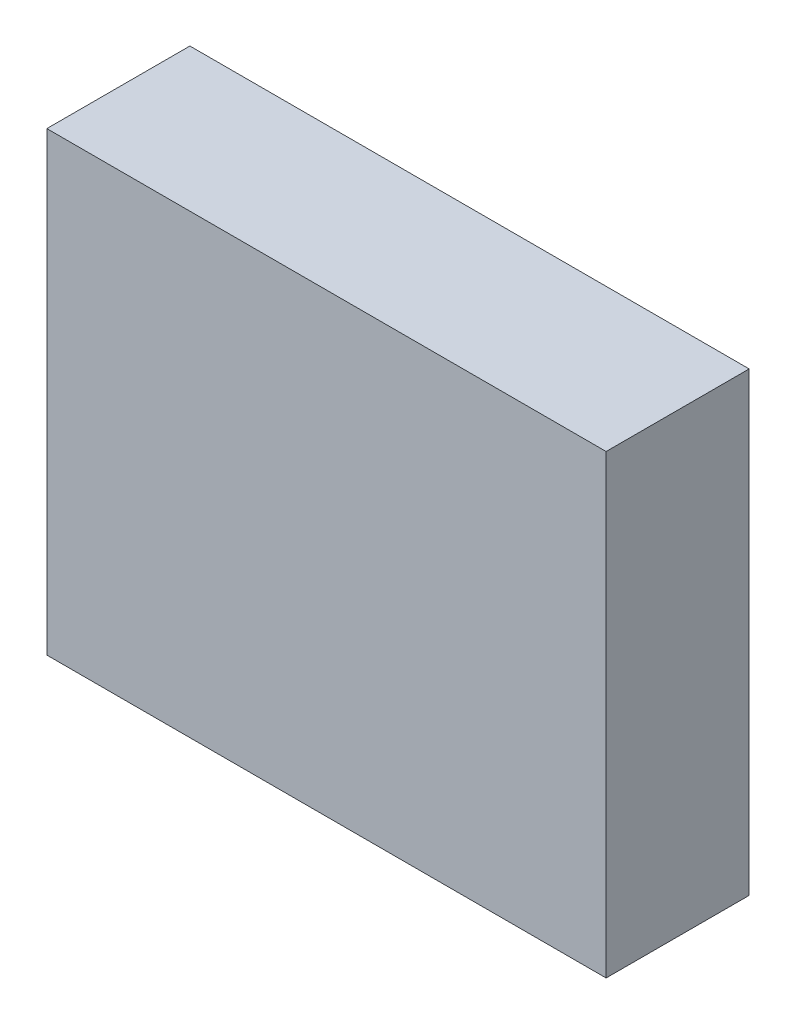
SolidWorks part; units mm, degrees
material "Aço"
ref_plane "Plano superior" through (0, 0, 0) normal (0, 0, 1) x (1, 0, 0)
ref_plane "Plano frontal" through (0, 0, 0) normal (0, 1, 0) x (1, 0, 0)
ref_plane "Plano direito" through (0, 0, 0) normal (1, 0, 0) x (0, 0, -1)
other "Caixa delimitadora"
ref_plane "Default Plane" through (-78.1989, -63.94, 0) normal (0, 1, 0) x (1, 0, 0)
sketch "Esboço1" plane through (0, 0, 0) normal (0, 0, 1) x (1, 0, 0)
  line L1 (-78.1989, -63.755) -> (78.1989, -63.755)
  line L2 (-78.1989, -63.755) -> (-78.1989, 63.755)
  line L3 (-78.1989, 63.755) -> (78.1989, 63.755)
  line L4 (78.1989, -63.755) -> (78.1989, 63.755)
  line L5 (-78.1989, -63.755) -> (78.1989, 63.755) construction
  line L6 (-78.1989, 63.755) -> (78.1989, -63.755) construction
  circle A0 centre (0, 0) radius 15.125 construction
  point P0 (0, 0)
  dimension "D3" = 30.25
  dimension "D1" = 156.3979
  dimension "D2" = 127.51
extrude "Ressalto-extrusão1" add sketch "Esboço1" along normal blind 40
